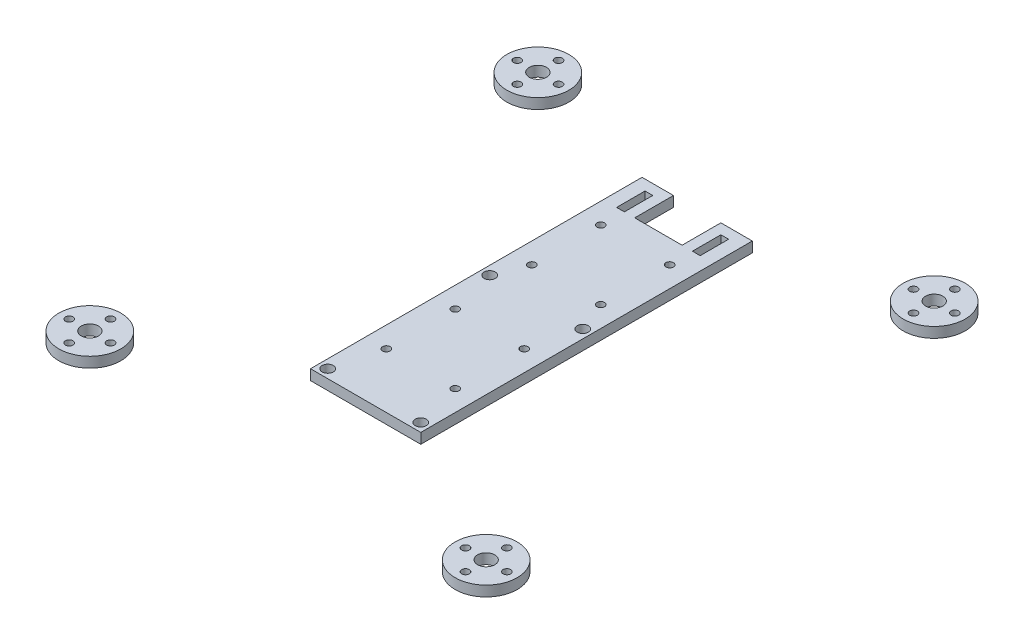
SolidWorks part; units mm, degrees
ref_plane "Front Plane" through (0, 0, 0) normal (0, 0, 1) x (1, 0, 0)
ref_plane "Top Plane" through (0, 0, 0) normal (0, 1, 0) x (1, 0, 0)
ref_plane "Right Plane" through (0, 0, 0) normal (1, 0, 0) x (0, 0, -1)
sketch "Sketch1" plane through (0, 0, 0) normal (0, 1, 0) x (1, 0, 0)
  line L0 (0, 42.475) -> (0, -42.475) construction
  line L1 (16, 42.475) -> (-16, 42.475)
  line L2 (16, 42.475) -> (16, -42.475)
  line L3 (16, -42.475) -> (-16, -42.475)
  line L4 (-16, 42.475) -> (-16, -42.475)
  line L5 (16, 42.475) -> (-16, -42.475) construction
  line L6 (16, -42.475) -> (-16, 42.475) construction
  line L8 (57.5, -65) -> (-57.5, -65)
  line L9 (57.5, -65) -> (57.5, 65)
  line L10 (57.5, 65) -> (-57.5, 65)
  line L11 (-57.5, -65) -> (-57.5, 65)
  line L12 (57.5, -65) -> (-57.5, 65) construction
  line L13 (57.5, 65) -> (-57.5, -65) construction
  line L17 (-11, 53.725) -> (-11, 42.475) construction
  line L18 (-6.875, 42.475) -> (-15.125, 42.475)
  line L19 (-57.5, 65) -> (0, 42.475) construction
  line L20 (-10, 35.75) -> (10, 35.75)
  line L21 (-10, 35.75) -> (-10, 15.75)
  line L22 (-10, 15.75) -> (10, 15.75)
  line L23 (10, 35.75) -> (10, 15.75)
  line L24 (-10, 35.75) -> (10, 15.75) construction
  line L25 (-10, 15.75) -> (10, 35.75) construction
  line L26 (-14.5, 10.525) -> (14.5, 10.525)
  line L27 (-14.5, 10.525) -> (-14.5, 40.975)
  line L28 (-14.5, 40.975) -> (14.5, 40.975)
  line L29 (14.5, 10.525) -> (14.5, 40.975)
  line L30 (-14.5, 10.525) -> (14.5, 40.975) construction
  line L31 (-14.5, 40.975) -> (14.5, 10.525) construction
  line L32 (-10, -6.475) -> (10, -6.475)
  line L33 (-10, -6.475) -> (-10, -26.475)
  line L34 (-10, -26.475) -> (10, -26.475)
  line L35 (10, -6.475) -> (10, -26.475)
  line L36 (-10, -6.475) -> (10, -26.475) construction
  line L37 (-10, -26.475) -> (10, -6.475) construction
  line L38 (-15.75, -36.475) -> (15.75, -36.475)
  line L39 (-15.75, -36.475) -> (-15.75, 3.525)
  line L40 (-15.75, 3.525) -> (15.75, 3.525)
  line L41 (15.75, -36.475) -> (15.75, 3.525)
  line L42 (-15.75, -36.475) -> (15.75, 3.525) construction
  line L43 (-15.75, 3.525) -> (15.75, -36.475) construction
  line L48 (-6.875, 42.475) -> (-6.875, 53.725)
  line L49 (-6.875, 53.725) -> (-15.125, 53.725)
  line L58 (-57.5, 0) -> (57.5, 0) construction
  line L59 (-15.125, 42.475) -> (-15.125, 53.725)
  line L63 (-12.125, 50.725) -> (-9.875, 50.725)
  line L64 (-12.125, 50.725) -> (-12.125, 42.475)
  line L65 (-12.125, 42.475) -> (-9.875, 42.475)
  line L66 (-9.875, 50.725) -> (-9.875, 42.475)
  line L67 (-12.125, 50.725) -> (-9.875, 42.475) construction
  line L68 (-12.125, 42.475) -> (-9.875, 50.725) construction
  line L69 (-12.125, 50.725) -> (-15.125, 50.725) construction
  line L71 (-12.125, 50.725) -> (-12.125, 53.725) construction
  line L74 (6.875, 42.475) -> (15.125, 42.475)
  line L75 (15.125, 42.475) -> (15.125, 53.725)
  line L76 (6.875, 53.725) -> (15.125, 53.725)
  line L77 (6.875, 42.475) -> (6.875, 53.725)
  line L78 (12.125, 50.725) -> (9.875, 50.725)
  line L79 (12.125, 50.725) -> (12.125, 42.475)
  line L80 (12.125, 42.475) -> (9.875, 42.475)
  line L81 (9.875, 50.725) -> (9.875, 42.475)
  line L82 (-14.5, 10.525) -> (-14.5, 3.525) construction
  line L83 (-14.5, 7.025) -> (16, 7.025) construction
  line L89 (-13.5, -37.475) -> (-16, -37.475) construction
  line L94 (-15.125, 53.725) -> (-16, 53.725)
  line L95 (-15.125, 53.725) -> (-15.125, 42.475)
  line L96 (-15.125, 42.475) -> (-16, 42.475)
  line L97 (-16, 53.725) -> (-16, 42.475)
  line L98 (15.125, 53.725) -> (16, 53.725)
  line L99 (15.125, 53.725) -> (15.125, 42.475)
  line L100 (15.125, 42.475) -> (16, 42.475)
  line L101 (16, 53.725) -> (16, 42.475)
  circle A0 centre (-57.5, 65) radius 36
  circle A1 centre (-57.5, 65) radius 6
  circle A2 centre (-57.5, 65) radius 9
  circle A3 centre (-10, 35.75) radius 1.1
  circle A4 centre (10, 35.75) radius 1.1
  circle A5 centre (10, 15.75) radius 1.1
  circle A6 centre (-10, 15.75) radius 1.1
  circle A7 centre (-10, -6.475) radius 1.1
  circle A8 centre (10, -6.475) radius 1.1
  circle A9 centre (10, -26.475) radius 1.1
  circle A10 centre (-10, -26.475) radius 1.1
  circle A11 centre (-57.5, 71) radius 1.1
  circle A12 centre (-63.5, 65) radius 1.1
  circle A13 centre (-57.5, 59) radius 1.1
  circle A14 centre (-51.5, 65) radius 1.1
  circle A15 centre (57.5, 59) radius 1.1
  circle A16 centre (51.5, 65) radius 1.1
  circle A17 centre (57.5, 71) radius 1.1
  circle A18 centre (63.5, 65) radius 1.1
  circle A19 centre (57.5, 65) radius 9
  circle A20 centre (57.5, -65) radius 9
  circle A21 centre (51.5, -65) radius 1.1
  circle A22 centre (57.5, -59) radius 1.1
  circle A23 centre (63.5, -65) radius 1.1
  circle A24 centre (57.5, -71) radius 1.1
  circle A25 centre (-57.5, -59) radius 1.1
  circle A26 centre (-51.5, -65) radius 1.1
  circle A27 centre (-57.5, -71) radius 1.1
  circle A28 centre (-63.5, -65) radius 1.1
  circle A29 centre (-57.5, -65) radius 9
  circle A30 centre (-57.5, -65) radius 36
  circle A31 centre (57.5, 65) radius 36
  circle A32 centre (57.5, -65) radius 36
  circle A33 centre (-57.5, 65) radius 2.5
  circle A34 centre (57.5, 65) radius 2.5
  circle A35 centre (57.5, -65) radius 2.5
  circle A36 centre (-57.5, -65) radius 2.5
  circle A37 centre (-13.5, 7.025) radius 2.5
  circle A38 centre (-13.5, 7.025) radius 1.625
  circle A39 centre (13.5, 7.025) radius 1.625
  circle A40 centre (-13.5, -39.975) radius 2.5
  circle A41 centre (-13.5, -39.975) radius 1.625
  circle A42 centre (13.5, -39.975) radius 1.625
  point P0 (0, 0)
  point P8 (0, 0)
  point P16 (0, 25.75)
  point P26 (0, 25.75)
  point P31 (0, -16.475)
  point P36 (0, -16.475)
  point P61 (-11, 46.6)
  dimension "D3" = 72
  dimension "D4" = 12
  dimension "D5" = 3
  dimension "D17" = 2.2
  dimension "D19" = 5
  dimension "D22" = 5
  dimension "D23" = 3.25
  dimension "D6" = 115
  dimension "D7" = 130
  dimension "D8" = 32
  dimension "D9" = 22
  dimension "D10" = 20
  dimension "D11" = 29
  dimension "D12" = 30.45
  dimension "D13" = 40
  dimension "D14" = 31.5
  dimension "D15" = 1.5
  dimension "D16" = 7
  dimension "D18" = 2.25
  dimension "D20" = 8.25
  dimension "D21" = 3
  dimension "D24" = 1
extrude "Boss-Extrude1" add sketch "Sketch1" along normal blind 3 contours L63 L66 L1 L48 L49 L59 L18 L64 | L81 L78 L79 L1 L75 L76 L77 | L94 L97 L1 L59 | L101 L98 L75 L1 | A2 | A11 | A14 | A13 | A12 | A19 | A15 | A18 | A17 | A16 | L1 L4 L3 L2 | A29 | A27 | A28 | A25 | A26 | A20 | A24 | A21 | A22 | A23 | A4 | A3 | A7 | A8 | A9 | A10 | A5 | A6 | A33 | A34 | A35 | A36 | A39 | A38 | A41 | A42 region at (15.5625, 0, -48.1) region at (13.625, 0, -42.6145) region at (-8.375, 0, -42.6145) region at (-15.5625, 0, -48.1)
